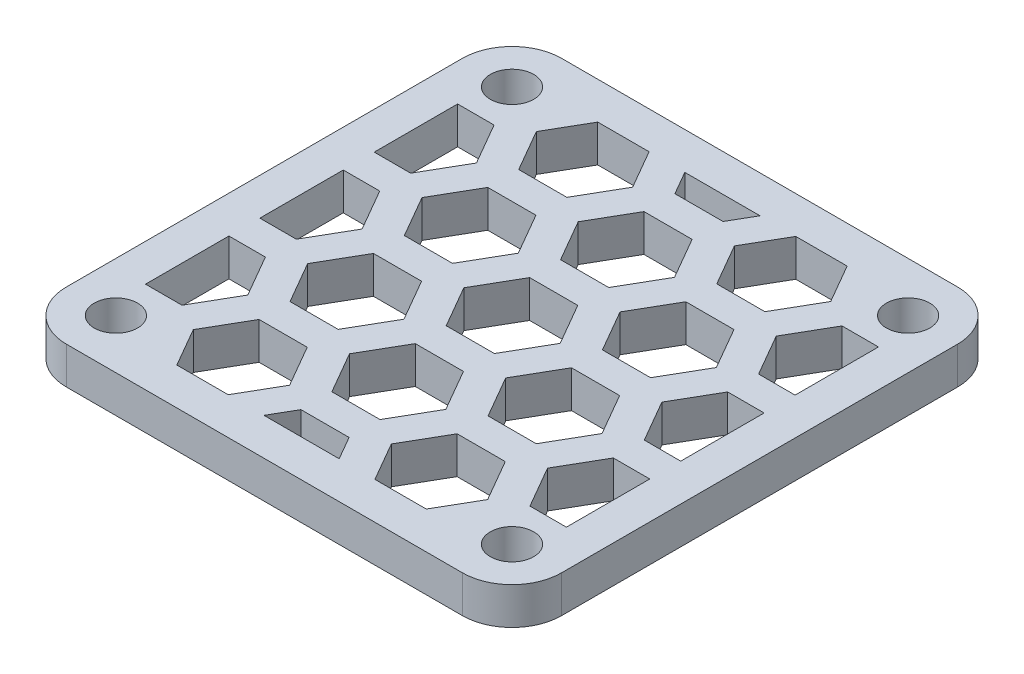
SolidWorks part; units mm, degrees
ref_plane "Front Plane" through (0, 0, 0) normal (0, 0, 1) x (1, 0, 0)
ref_plane "Top Plane" through (0, 0, 0) normal (0, 1, 0) x (1, 0, 0)
ref_plane "Right Plane" through (0, 0, 0) normal (1, 0, 0) x (0, 0, -1)
sketch "Sketch1" plane through (0, 0, 0) normal (0, 1, 0) x (1, 0, 0)
  line L1 (-16, -20) -> (16, -20)
  line L2 (-20, -16) -> (-20, 16)
  line L3 (-16, 20) -> (16, 20)
  line L4 (20, -16) -> (20, 16)
  line L5 (-18.8284, -18.8284) -> (16, 16) construction
  line L6 (-16, 16) -> (18.8284, -18.8284) construction
  circle A0 centre (-16, 16) radius 1.75
  circle A1 centre (16, 16) radius 1.75
  circle A2 centre (16, -16) radius 1.75
  circle A3 centre (-16, -16) radius 1.75
  arc A4 (-20, 16) -> (-16, 20) centre (-16, 16) cw
  arc A5 (16, 20) -> (20, 16) centre (16, 16) cw
  arc A6 (-16, -20) -> (-20, -16) centre (-16, -16) cw
  arc A7 (16, -20) -> (20, -16) centre (16, -16) ccw
  point P0 (0, 0)
  point P4 (20, 10.22)
  dimension "D2" = 3.5
  dimension "D1" = 40
  dimension "D3" = 32
extrude "Boss-Extrude1" add sketch "Sketch1" along normal blind 3 contours L1 A7 L4 A5 L3 A4 L2 A6 A0 A1 A2 A3 | A0 | A1 | A2 | A3 region at (0, 0, 0) region at (-16, 0, -16) region at (16, 0, -16) region at (16, 0, 16) region at (-16, 0, 16)
sketch "Sketch2" plane through (0, 0, 0) normal (0, 1, 0) x (1, 0, 0)
  line L0 (5.0825, -2.9344) -> (2.9175, -1.6844) construction
  line L1 (1.945, -3.3688) -> (3.89, 0)
  line L2 (3.89, 0) -> (1.945, 3.3688)
  line L3 (1.945, 3.3688) -> (-1.945, 3.3688)
  line L4 (-1.945, 3.3688) -> (-3.89, 0)
  line L5 (-3.89, 0) -> (-1.945, -3.3688)
  line L6 (-1.945, -3.3688) -> (1.945, -3.3688)
  line L7 (9.945, -7.9876) -> (11.89, -4.6188)
  line L8 (11.89, -4.6188) -> (9.945, -1.25)
  line L9 (9.945, -1.25) -> (6.055, -1.25)
  line L10 (6.055, -1.25) -> (4.11, -4.6188)
  line L11 (4.11, -4.6188) -> (6.055, -7.9876)
  line L12 (6.055, -7.9876) -> (9.945, -7.9876)
  line L13 (2.9175, 1.6844) -> (5.0825, 2.9344) construction
  line L14 (9.945, 1.25) -> (11.89, 4.6188)
  line L15 (11.89, 4.6188) -> (9.945, 7.9876)
  line L16 (9.945, 7.9876) -> (6.055, 7.9876)
  line L17 (6.055, 7.9876) -> (4.11, 4.6188)
  line L18 (4.11, 4.6188) -> (6.055, 1.25)
  line L19 (6.055, 1.25) -> (9.945, 1.25)
  circle A0 centre (0, 0) radius 3.3688 construction
  circle A1 centre (8, -4.6188) radius 3.3688 construction
  circle A2 centre (8, 4.6188) radius 3.3688 construction
  point P29 (6.0398, 1.0858)
  dimension "D1" = 2.5
  dimension "D2" = 8
  dimension "D3" = 4.6188
sketch "Sketch3" plane through (0, 0, 0) normal (0, 1, 0) x (1, 0, 0)
  line L0 (6.055, -1.25) -> (4.11, -4.6188) construction
  line L1 (4.11, -4.6188) -> (6.055, -7.9876) construction
  line L2 (6.055, -7.9876) -> (9.945, -7.9876) construction
  line L3 (9.945, -7.9876) -> (11.89, -4.6188) construction
  line L4 (11.89, -4.6188) -> (9.945, -1.25) construction
  line L5 (9.945, -1.25) -> (6.055, -1.25) construction
  line L6 (-1.945, 3.3688) -> (-3.89, 0) construction
  line L7 (-3.89, 0) -> (-1.945, -3.3688) construction
  line L8 (-1.945, -3.3688) -> (1.945, -3.3688) construction
  line L9 (1.945, -3.3688) -> (3.89, 0) construction
  line L10 (3.89, 0) -> (1.945, 3.3688) construction
  line L11 (1.945, 3.3688) -> (-1.945, 3.3688) construction
  line L12 (6.055, -1.25) -> (4.11, -4.6188)
  line L13 (4.11, -4.6188) -> (6.055, -7.9876)
  line L14 (6.055, -7.9876) -> (9.945, -7.9876)
  line L15 (9.945, -7.9876) -> (11.89, -4.6188)
  line L16 (11.89, -4.6188) -> (9.945, -1.25)
  line L17 (9.945, -1.25) -> (6.055, -1.25)
  line L18 (-1.945, 3.3688) -> (-3.89, 0)
  line L19 (-3.89, 0) -> (-1.945, -3.3688)
  line L20 (-1.945, -3.3688) -> (1.945, -3.3688)
  line L21 (1.945, -3.3688) -> (3.89, 0)
  line L22 (3.89, 0) -> (1.945, 3.3688)
  line L23 (1.945, 3.3688) -> (-1.945, 3.3688)
  line L24 (14.055, 3.3688) -> (12.11, 0)
  line L25 (12.11, 0) -> (14.055, -3.3688)
  line L26 (14.055, -3.3688) -> (17.945, -3.3688)
  line L27 (17.945, -3.3688) -> (19.89, 0)
  line L28 (19.89, 0) -> (17.945, 3.3688)
  line L29 (17.945, 3.3688) -> (14.055, 3.3688)
  line L30 (22.055, -1.25) -> (20.11, -4.6188)
  line L31 (20.11, -4.6188) -> (22.055, -7.9876)
  line L32 (22.055, -7.9876) -> (25.945, -7.9876)
  line L33 (25.945, -7.9876) -> (27.89, -4.6188)
  line L34 (27.89, -4.6188) -> (25.945, -1.25)
  line L35 (25.945, -1.25) -> (22.055, -1.25)
  line L36 (14.055, 12.6064) -> (12.11, 9.2376)
  line L37 (12.11, 9.2376) -> (14.055, 5.8688)
  line L38 (14.055, 5.8688) -> (17.945, 5.8688)
  line L39 (17.945, 5.8688) -> (19.89, 9.2376)
  line L40 (19.89, 9.2376) -> (17.945, 12.6064)
  line L41 (17.945, 12.6064) -> (14.055, 12.6064)
  line L42 (22.055, 7.9876) -> (20.11, 4.6188)
  line L43 (20.11, 4.6188) -> (22.055, 1.25)
  line L44 (22.055, 1.25) -> (25.945, 1.25)
  line L45 (25.945, 1.25) -> (27.89, 4.6188)
  line L46 (27.89, 4.6188) -> (25.945, 7.9876)
  line L47 (25.945, 7.9876) -> (22.055, 7.9876)
  line L48 (14.055, 21.844) -> (12.11, 18.4752)
  line L49 (12.11, 18.4752) -> (14.055, 15.1064)
  line L50 (14.055, 15.1064) -> (17.945, 15.1064)
  line L51 (17.945, 15.1064) -> (19.89, 18.4752)
  line L52 (19.89, 18.4752) -> (17.945, 21.844)
  line L53 (17.945, 21.844) -> (14.055, 21.844)
  line L54 (22.055, 17.2252) -> (20.11, 13.8564)
  line L55 (20.11, 13.8564) -> (22.055, 10.4876)
  line L56 (22.055, 10.4876) -> (25.945, 10.4876)
  line L57 (25.945, 10.4876) -> (27.89, 13.8564)
  line L58 (27.89, 13.8564) -> (25.945, 17.2252)
  line L59 (25.945, 17.2252) -> (22.055, 17.2252)
  line L60 (-1.945, 12.6064) -> (-3.89, 9.2376)
  line L61 (-3.89, 9.2376) -> (-1.945, 5.8688)
  line L62 (-1.945, 5.8688) -> (1.945, 5.8688)
  line L63 (1.945, 5.8688) -> (3.89, 9.2376)
  line L64 (3.89, 9.2376) -> (1.945, 12.6064)
  line L65 (1.945, 12.6064) -> (-1.945, 12.6064)
  line L66 (6.055, 7.9876) -> (4.11, 4.6188)
  line L67 (4.11, 4.6188) -> (6.055, 1.25)
  line L68 (6.055, 1.25) -> (9.945, 1.25)
  line L69 (9.945, 1.25) -> (11.89, 4.6188)
  line L70 (11.89, 4.6188) -> (9.945, 7.9876)
  line L71 (9.945, 7.9876) -> (6.055, 7.9876)
  line L72 (-1.945, 21.844) -> (-3.89, 18.4752)
  line L73 (-3.89, 18.4752) -> (-1.945, 15.1064)
  line L74 (-1.945, 15.1064) -> (1.945, 15.1064)
  line L75 (1.945, 15.1064) -> (3.89, 18.4752)
  line L76 (3.89, 18.4752) -> (1.945, 21.844)
  line L77 (1.945, 21.844) -> (-1.945, 21.844)
  line L78 (6.055, 17.2252) -> (4.11, 13.8564)
  line L79 (4.11, 13.8564) -> (6.055, 10.4876)
  line L80 (6.055, 10.4876) -> (9.945, 10.4876)
  line L81 (9.945, 10.4876) -> (11.89, 13.8564)
  line L82 (11.89, 13.8564) -> (9.945, 17.2252)
  line L83 (9.945, 17.2252) -> (6.055, 17.2252)
  line L84 (-1.945, 3.3688) -> (14.055, 3.3688) construction
  line L85 (-1.945, 3.3688) -> (-1.945, 12.6064) construction
  line L86 (0, 20) -> (0, -20) construction
  line L89 (-9.945, -1.25) -> (-6.055, -1.25)
  line L90 (-11.89, -4.6188) -> (-9.945, -1.25)
  line L91 (-9.945, -7.9876) -> (-11.89, -4.6188)
  line L92 (-6.055, -7.9876) -> (-9.945, -7.9876)
  line L93 (-4.11, -4.6188) -> (-6.055, -7.9876)
  line L94 (-6.055, -1.25) -> (-4.11, -4.6188)
  line L95 (-9.945, 7.9876) -> (-6.055, 7.9876)
  line L96 (-11.89, 4.6188) -> (-9.945, 7.9876)
  line L97 (-9.945, 1.25) -> (-11.89, 4.6188)
  line L98 (-6.055, 1.25) -> (-9.945, 1.25)
  line L99 (-4.11, 4.6188) -> (-6.055, 1.25)
  line L100 (-6.055, 7.9876) -> (-4.11, 4.6188)
  line L101 (-9.945, 17.2252) -> (-6.055, 17.2252)
  line L102 (-11.89, 13.8564) -> (-9.945, 17.2252)
  line L103 (-9.945, 10.4876) -> (-11.89, 13.8564)
  line L104 (-6.055, 10.4876) -> (-9.945, 10.4876)
  line L105 (-4.11, 13.8564) -> (-6.055, 10.4876)
  line L106 (-6.055, 17.2252) -> (-4.11, 13.8564)
  line L107 (-17.945, 12.6064) -> (-14.055, 12.6064)
  line L108 (-19.89, 9.2376) -> (-17.945, 12.6064)
  line L109 (-17.945, 5.8688) -> (-19.89, 9.2376)
  line L110 (-14.055, 5.8688) -> (-17.945, 5.8688)
  line L111 (-12.11, 9.2376) -> (-14.055, 5.8688)
  line L112 (-14.055, 12.6064) -> (-12.11, 9.2376)
  line L113 (-17.945, 3.3688) -> (-14.055, 3.3688)
  line L114 (-19.89, 0) -> (-17.945, 3.3688)
  line L115 (-17.945, -3.3688) -> (-19.89, 0)
  line L116 (-14.055, -3.3688) -> (-17.945, -3.3688)
  line L117 (-12.11, 0) -> (-14.055, -3.3688)
  line L118 (-14.055, 3.3688) -> (-12.11, 0)
  line L119 (-25.945, -1.25) -> (-22.055, -1.25)
  line L120 (-27.89, -4.6188) -> (-25.945, -1.25)
  line L121 (-25.945, -7.9876) -> (-27.89, -4.6188)
  line L122 (-22.055, -7.9876) -> (-25.945, -7.9876)
  line L123 (-20.11, -4.6188) -> (-22.055, -7.9876)
  line L124 (-22.055, -1.25) -> (-20.11, -4.6188)
  line L125 (-25.945, 7.9876) -> (-22.055, 7.9876)
  line L126 (-27.89, 4.6188) -> (-25.945, 7.9876)
  line L127 (-25.945, 1.25) -> (-27.89, 4.6188)
  line L128 (-22.055, 1.25) -> (-25.945, 1.25)
  line L129 (-20.11, 4.6188) -> (-22.055, 1.25)
  line L130 (-22.055, 7.9876) -> (-20.11, 4.6188)
  line L131 (-25.945, 17.2252) -> (-22.055, 17.2252)
  line L132 (-27.89, 13.8564) -> (-25.945, 17.2252)
  line L133 (-25.945, 10.4876) -> (-27.89, 13.8564)
  line L134 (-22.055, 10.4876) -> (-25.945, 10.4876)
  line L135 (-20.11, 13.8564) -> (-22.055, 10.4876)
  line L136 (-22.055, 17.2252) -> (-20.11, 13.8564)
  line L137 (-17.945, 21.844) -> (-14.055, 21.844)
  line L138 (-19.89, 18.4752) -> (-17.945, 21.844)
  line L139 (-17.945, 15.1064) -> (-19.89, 18.4752)
  line L140 (-14.055, 15.1064) -> (-17.945, 15.1064)
  line L141 (-12.11, 18.4752) -> (-14.055, 15.1064)
  line L142 (-14.055, 21.844) -> (-12.11, 18.4752)
  line L143 (0, 0) -> (20, 0) construction
  line L145 (17.945, -21.844) -> (14.055, -21.844)
  line L146 (19.89, -18.4752) -> (17.945, -21.844)
  line L147 (17.945, -15.1064) -> (19.89, -18.4752)
  line L148 (14.055, -15.1064) -> (17.945, -15.1064)
  line L149 (12.11, -18.4752) -> (14.055, -15.1064)
  line L150 (14.055, -21.844) -> (12.11, -18.4752)
  line L151 (25.945, -17.2252) -> (22.055, -17.2252)
  line L152 (27.89, -13.8564) -> (25.945, -17.2252)
  line L153 (25.945, -10.4876) -> (27.89, -13.8564)
  line L154 (22.055, -10.4876) -> (25.945, -10.4876)
  line L155 (20.11, -13.8564) -> (22.055, -10.4876)
  line L156 (22.055, -17.2252) -> (20.11, -13.8564)
  line L157 (17.945, -12.6064) -> (14.055, -12.6064)
  line L158 (19.89, -9.2376) -> (17.945, -12.6064)
  line L159 (17.945, -5.8688) -> (19.89, -9.2376)
  line L160 (14.055, -5.8688) -> (17.945, -5.8688)
  line L161 (12.11, -9.2376) -> (14.055, -5.8688)
  line L162 (14.055, -12.6064) -> (12.11, -9.2376)
  line L163 (9.945, -17.2252) -> (6.055, -17.2252)
  line L164 (11.89, -13.8564) -> (9.945, -17.2252)
  line L165 (9.945, -10.4876) -> (11.89, -13.8564)
  line L166 (6.055, -10.4876) -> (9.945, -10.4876)
  line L167 (4.11, -13.8564) -> (6.055, -10.4876)
  line L168 (6.055, -17.2252) -> (4.11, -13.8564)
  line L169 (1.945, -21.844) -> (-1.945, -21.844)
  line L170 (3.89, -18.4752) -> (1.945, -21.844)
  line L171 (1.945, -15.1064) -> (3.89, -18.4752)
  line L172 (-1.945, -15.1064) -> (1.945, -15.1064)
  line L173 (-3.89, -18.4752) -> (-1.945, -15.1064)
  line L174 (-1.945, -21.844) -> (-3.89, -18.4752)
  line L175 (1.945, -12.6064) -> (-1.945, -12.6064)
  line L176 (3.89, -9.2376) -> (1.945, -12.6064)
  line L177 (1.945, -5.8688) -> (3.89, -9.2376)
  line L178 (-1.945, -5.8688) -> (1.945, -5.8688)
  line L179 (-3.89, -9.2376) -> (-1.945, -5.8688)
  line L180 (-1.945, -12.6064) -> (-3.89, -9.2376)
  line L181 (-11.89, -13.8564) -> (-9.945, -17.2252)
  line L182 (-9.945, -10.4876) -> (-11.89, -13.8564)
  line L183 (-6.055, -10.4876) -> (-9.945, -10.4876)
  line L184 (-4.11, -13.8564) -> (-6.055, -10.4876)
  line L185 (-6.055, -17.2252) -> (-4.11, -13.8564)
  line L186 (-9.945, -17.2252) -> (-6.055, -17.2252)
  line L187 (-19.89, -18.4752) -> (-17.945, -21.844)
  line L188 (-17.945, -15.1064) -> (-19.89, -18.4752)
  line L189 (-14.055, -15.1064) -> (-17.945, -15.1064)
  line L190 (-12.11, -18.4752) -> (-14.055, -15.1064)
  line L191 (-14.055, -21.844) -> (-12.11, -18.4752)
  line L192 (-17.945, -21.844) -> (-14.055, -21.844)
  line L193 (-27.89, -13.8564) -> (-25.945, -17.2252)
  line L194 (-25.945, -10.4876) -> (-27.89, -13.8564)
  line L195 (-22.055, -10.4876) -> (-25.945, -10.4876)
  line L196 (-20.11, -13.8564) -> (-22.055, -10.4876)
  line L197 (-22.055, -17.2252) -> (-20.11, -13.8564)
  line L198 (-25.945, -17.2252) -> (-22.055, -17.2252)
  line L199 (-19.89, -9.2376) -> (-17.945, -12.6064)
  line L200 (-17.945, -5.8688) -> (-19.89, -9.2376)
  line L201 (-14.055, -5.8688) -> (-17.945, -5.8688)
  line L202 (-12.11, -9.2376) -> (-14.055, -5.8688)
  line L203 (-14.055, -12.6064) -> (-12.11, -9.2376)
  line L204 (-17.945, -12.6064) -> (-14.055, -12.6064)
  line L205 (20, -16) -> (20, 16) construction
  line L206 (-16, 20) -> (16, 20) construction
  line L207 (-16, -20) -> (16, -20) construction
  point P81 (0, 20)
  point P83 (0, -20)
  point P135 (0, 0)
  point P136 (0, 0)
  point P137 (0, 0)
  point P199 (0, 0)
  point P200 (0, 0)
  point P201 (0, 0)
  point P202 (20, 0)
  point P205 (0, 0)
  point P207 (0, 0)
  dimension "D3" = 16
  dimension "D4" = 9.2376
  dimension "D1" = 2
  dimension "D2" = 3
extrude "Cut-Extrude1" cut sketch "Sketch3" along normal through all
sketch "Sketch4" plane through (0, 0, 0) normal (0, 1, 0) x (1, 0, 0)
  line L0 (12.9617, 17) -> (-12.9617, 17)
  line L1 (-17, 15.1064) -> (-17, -15.1064)
  line L2 (-12.9617, -17) -> (12.9617, -17)
  line L3 (17, -15.1064) -> (17, 15.1064)
  line L4 (-20, 16) -> (-20, -16)
  line L5 (16, 20) -> (-16, 20)
  line L6 (20, -16) -> (20, 16)
  line L7 (-16, -20) -> (16, -20)
  line L8 (-20, 16) -> (-20, -16)
  line L9 (16, 20) -> (-16, 20)
  line L10 (20, -16) -> (20, 16)
  line L11 (-16, -20) -> (16, -20)
  line L12 (-14.055, -15.1064) -> (-17.945, -15.1064) construction
  line L13 (-12.11, -18.4752) -> (-14.055, -15.1064) construction
  line L14 (14.055, -15.1064) -> (12.11, -18.4752) construction
  line L15 (17.945, -15.1064) -> (14.055, -15.1064) construction
  line L16 (12.11, 18.4752) -> (14.055, 15.1064) construction
  line L17 (14.055, 15.1064) -> (17.945, 15.1064) construction
  line L18 (-17.945, 15.1064) -> (-14.055, 15.1064) construction
  line L19 (-14.055, 15.1064) -> (-12.11, 18.4752) construction
  line L20 (-14.055, -15.1064) -> (-17, -15.1064)
  line L21 (-12.9617, -17) -> (-14.055, -15.1064)
  line L22 (14.055, -15.1064) -> (12.9617, -17)
  line L23 (17, -15.1064) -> (14.055, -15.1064)
  line L24 (12.9617, 17) -> (14.055, 15.1064)
  line L25 (14.055, 15.1064) -> (17, 15.1064)
  line L26 (-17, 15.1064) -> (-14.055, 15.1064)
  line L27 (-14.055, 15.1064) -> (-12.9617, 17)
  line L28 (16, 17) -> (-16, 17) construction
  line L29 (-17, 16) -> (-17, -16) construction
  line L30 (17, -16) -> (17, 16) construction
  line L31 (-16, -17) -> (16, -17) construction
  arc A12 (-16, 20) -> (-20, 16) centre (-16, 16) ccw
  arc A13 (20, 16) -> (16, 20) centre (16, 16) ccw
  arc A14 (16, -20) -> (20, -16) centre (16, -16) ccw
  arc A15 (-20, -16) -> (-16, -20) centre (-16, -16) ccw
  arc A16 (-16, 20) -> (-20, 16) centre (-16, 16) ccw
  arc A17 (20, 16) -> (16, 20) centre (16, 16) ccw
  arc A18 (16, -20) -> (20, -16) centre (16, -16) ccw
  arc A19 (-20, -16) -> (-16, -20) centre (-16, -16) ccw
  arc A20 (-16, 17) -> (-17, 16) centre (-16, 16) ccw construction
  arc A21 (17, 16) -> (16, 17) centre (16, 16) ccw construction
  arc A22 (-17, -16) -> (-16, -17) centre (-16, -16) ccw construction
  arc A23 (16, -17) -> (17, -16) centre (16, -16) ccw construction
  dimension "D5" = 0
  dimension "D6" = 3
extrude "Boss-Extrude2" add sketch "Sketch4" along normal through all
extrude "Cut-Extrude2" cut sketch "Sketch1<3>" along normal through all contours A1 | A3 | A2 | A0 region at (16, 0, -16) region at (16, 0, 16) region at (-16, 0, 16)
sketch "Sketch1<3>" plane through (0, 0, 0) normal (0, 1, 0) x (1, 0, 0) same geometry as "Sketch1"
